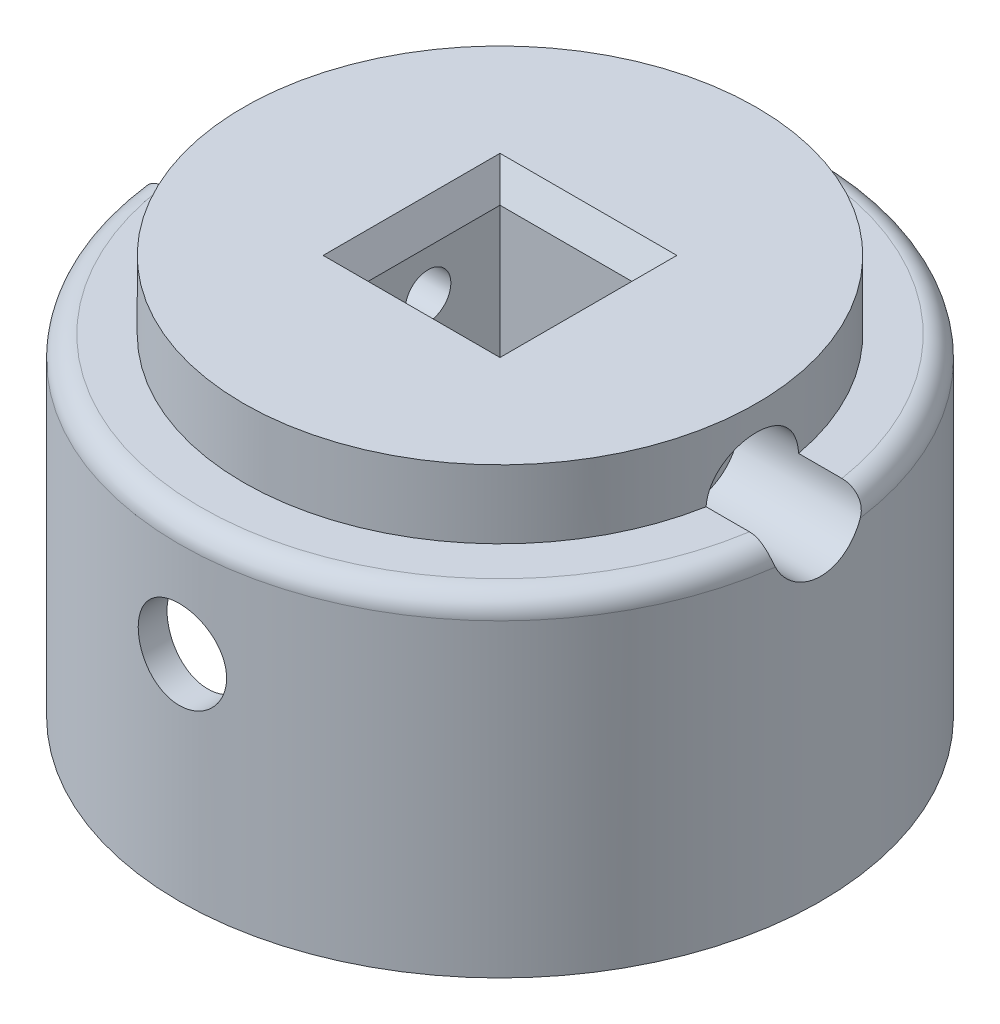
SolidWorks part; units mm, degrees
ref_plane "Спереди" through (0, 0, 0) normal (0, 0, 1) x (1, 0, 0)
ref_plane "Сверху" through (0, 0, 0) normal (0, 1, 0) x (1, 0, 0)
ref_plane "Справа" through (0, 0, 0) normal (1, 0, 0) x (0, 0, -1)
sketch "Sketch1" plane through (0, 0, 0) normal (0, 1, 0) x (1, 0, 0)
  circle A0 centre (0, 0) radius 22.5
  dimension "D1" = 45
extrude "Boss-Extrude1" add sketch "Sketch1" along normal blind 28
sketch "Sketch2" plane through (0, 0, 0) normal (0, -1, 0) x (1, 0, 0)
  line L1 (5.05, 5.05) -> (-5.05, 5.05)
  line L2 (5.05, 5.05) -> (5.05, -5.05)
  line L3 (5.05, -5.05) -> (-5.05, -5.05)
  line L4 (-5.05, 5.05) -> (-5.05, -5.05)
  line L5 (5.05, 5.05) -> (-5.05, -5.05) construction
  line L6 (5.05, -5.05) -> (-5.05, 5.05) construction
  point P0 (0, 0)
  dimension "D1" = 10.1
extrude "Cut-Extrude2" cut sketch "Sketch2" against normal through all
shell "Shell3" thickness 2 removed face at (0, 0, 0)
sketch "Sketch3" plane through (0, 0, 7.05) normal (0, 0, 1) x (1, 0, 0)
  line L0 (0, 26) -> (0, 0) construction
  line L1 (7.05, 26) -> (-7.05, 26) construction
  line L2 (7.05, 0) -> (-7.05, 0) construction
  line L3 (-22.5, 0) -> (22.5, 0) construction
  circle A0 centre (0, 15) radius 3.1
  dimension "D1" = 6.2
  dimension "D2" = 15
extrude "Cut-Extrude3" cut sketch "Sketch3" along normal through all
chamfer "Chamfer1" distance 2 angle 30 4 edges at (-5.05, 28, 0) (0, 28, 5.05) (5.05, 28, 0) (0, 28, -5.05) first distance on face at (-5.05, 14, 0) first distance on face at (0, 14, 5.05) first distance on face at (5.05, 14, 0) first distance on face at (0, 14, -5.05)
sketch "Sketch18" plane through (0, 26, 0) normal (0, -1, 0) x (1, 0, 0)
  line L0 (0, 0) -> (-18.4253, -8.9866) construction
  line L1 (0, 0) -> (-17.385, 10.8633) construction
  line L2 (0, 0) -> (0, -20.5) construction
  line L3 (-15.7289, -7.6715) -> (-18.4253, -8.9866)
  line L4 (-14.8408, 9.2736) -> (-17.385, 10.8633)
  circle A0 centre (0, 0) radius 20.5 construction
  arc A1 (-18.4253, -8.9866) -> (-17.385, 10.8633) centre (0, 0) cw
  arc A2 (-14.8408, 9.2736) -> (-15.7289, -7.6715) centre (0, 0) ccw
  dimension "D1" = 64
  dimension "D2" = 58
  dimension "D3" = 3
extrude "Boss-Extrude8" add sketch "Sketch18" along normal offset from surface (23 mm away) 3 up to face at (0, 0, 20.5)
sketch "Sketch9" plane through (0, 0, 0) normal (0, -1, 0) x (1, 0, 0)
  line L0 (0, -7.05) -> (0, -20.5) construction
  line L2 (2.0704, -22.4045) -> (-16.5877, -15.202)
  line L3 (-16.5877, -15.202) -> (-17.6681, -18.0007)
  line L4 (-17.6681, -18.0007) -> (0.99, -25.2032)
  line L5 (0.99, -25.2032) -> (2.0704, -22.4045)
  line L6 (-7.05, -7.05) -> (7.05, -7.05) construction
  line L7 (2.0704, -22.4045) -> (0, -7.05) construction
  circle A0 centre (0, 0) radius 22.5 construction
  circle A1 centre (0, 0) radius 20.5 construction
  dimension "D1" = 20
  dimension "D2" = 3
  dimension "D3" = 7.679
extrude "Boss-Extrude4" add sketch "Sketch9" against normal blind 20
sketch "Sketch11" plane through (0, 0, 0) normal (0, -1, 0) x (1, 0, 0)
  line L0 (2.0704, -22.4045) -> (7.05, -7.05)
  line L1 (7.05, -7.05) -> (-7.05, -7.05)
  line L2 (-7.05, -7.05) -> (-16.5877, -15.202)
  line L3 (-16.5877, -15.202) -> (2.0704, -22.4045) construction
  line L4 (-3.768, -20.1507) -> (-10.7492, -17.4558) construction
  arc A0 (2.0704, -22.4045) -> (-16.5877, -15.202) centre (0, 0) ccw construction
  arc A1 (2.0704, -22.4045) -> (-16.5877, -15.202) centre (0, 0) cw
  arc A2 (2.0704, -22.4045) -> (-16.5877, -15.202) centre (0, 0) ccw construction
  point P4 (-7.2586, -18.8032)
extrude "Boss-Extrude6" add sketch "Sketch11" against normal up to surface (26 mm away) up to face at (0, 26, 0)
sketch "Sketch12" plane through (0, 0, 0) normal (0, -1, 0) x (1, 0, 0)
  line L0 (-7.05, -7.05) -> (-15.0663, -13.9016) construction
  line L1 (2.748, -20.315) -> (7.05, -7.05) construction
  line L2 (3.7952, -17.0861) -> (2.748, -20.315)
  line L3 (-15.0663, -13.9016) -> (-12.7858, -11.9525)
  arc A0 (2.748, -20.315) -> (-15.0663, -13.9016) centre (0, 0) cw
  arc A1 (-12.7858, -11.9525) -> (3.7952, -17.0861) centre (0, 0) ccw
  arc A2 (2.748, -20.315) -> (-15.0663, -13.9016) centre (0, 0) ccw construction
  dimension "D1" = 3
extrude "Cut-Extrude5" cut sketch "Sketch12" against normal blind 12
sketch "Sketch17" plane through (0, 0, 0) normal (0, -1, 0) x (1, 0, 0)
  line L0 (7.05, 7.05) -> (7.05, -7.05)
  line L1 (7.05, -7.05) -> (3.7952, -17.0861)
  line L2 (7.05, 7.05) -> (-7.05, 7.05)
  line L3 (-7.05, 7.05) -> (-7.05, -7.05)
  line L4 (-7.05, -7.05) -> (-12.7858, -11.9525)
  arc A0 (3.7952, -17.0861) -> (-12.7858, -11.9525) centre (0, 0) cw
  arc A1 (-12.7858, -11.9525) -> (3.7952, -17.0861) centre (0, 0) ccw construction
extrude "Cut-Extrude9" cut sketch "Sketch17" against normal blind 2
sketch "Sketch20" plane through (0, 26, 0) normal (0, -1, 0) x (1, 0, 0)
  line L0 (2.748, -20.315) -> (7.05, -7.05)
  line L1 (7.05, -7.05) -> (7.05, 7.05)
  line L2 (7.05, 7.05) -> (-7.05, 7.05)
  line L3 (-7.05, 7.05) -> (-7.05, -7.05)
  line L4 (-7.05, -7.05) -> (-15.0663, -13.9016)
  arc A0 (2.748, -20.315) -> (-15.0663, -13.9016) centre (0, 0) ccw
  arc A1 (2.748, -20.315) -> (-17.385, 10.8633) centre (0, 0) ccw construction
extrude "Boss-Extrude10" add sketch "Sketch20" along normal blind 7
sketch "Sketch21" plane through (0, 28, 0) normal (0, 1, 0) x (1, 0, 0)
  circle A0 centre (0, 0) radius 18
  dimension "D1" = 36
extrude "Cut-Extrude11" cut sketch "Sketch21" against normal blind 4.8 flip side to cut
sketch "Sketch22" plane through (5.05, 0, 0) normal (-1, 0, 0) x (0, 0, 1)
  line L0 (0, 26) -> (0, 2) construction
  line L1 (5.05, 26) -> (-5.05, 26) construction
  line L2 (-5.05, 2) -> (5.05, 2) construction
  line L3 (-6.2047, 28) -> (6.2047, 28) construction
  circle A0 centre (0, 23) radius 1.6
  point P10 (0, 28)
  dimension "D1" = 3.2
  dimension "D2" = 5
extrude "Cut-Extrude12" cut sketch "Sketch22" against normal through all both and the other way through all
sketch "Sketch24" plane through (5.05, 0, 0) normal (-1, 0, 0) x (0, 0, 1)
  circle A0 centre (0, 23) radius 3.25
  dimension "D1" = 6.5
extrude "Cut-Extrude13" cut sketch "Sketch24" against normal through all from offset 8.5 offset against normal yes
sketch "Sketch25" plane through (-5.05, 0, 0) normal (1, 0, 0) x (0, 0, -1)
  line L0 (-5.05, 26) -> (-5.05, 2) construction
  line L1 (0, 19.75) -> (2.8146, 21.375)
  line L2 (2.8146, 21.375) -> (2.8146, 24.625)
  line L3 (2.8146, 24.625) -> (0, 26.25)
  line L4 (0, 26.25) -> (-2.8146, 24.625)
  line L5 (-2.8146, 24.625) -> (-2.8146, 21.375)
  line L6 (-2.8146, 21.375) -> (0, 19.75)
  circle A0 centre (0, 23) radius 3.25 construction
  dimension "D1" = 6.5
extrude "Cut-Extrude14" cut sketch "Sketch25" against normal through all from offset 8.5 offset against normal yes
fillet "Fillet1" radius 1.5 2 edges at (-0.2166, 23.2, 22.499) (-0.2166, 23.2, -22.499)
sketch "Sketch26" plane through (0, 0, 0) normal (0, -1, 0) x (1, 0, 0)
  circle A0 centre (0, 0) radius 22.5
  arc A1 (2.0704, -22.4045) -> (-16.5877, -15.202) centre (0, 0) ccw construction
  circle A2 centre (0, 0) radius 43.9199
extrude "Cut-Extrude15" cut sketch "Sketch26" against normal through all
chamfer "Chamfer2" distance 0.5 angle 70 4 edges at (-5.05, 2, 0) (0, 2, 5.05) (0, 2, -5.05) (5.05, 2, 0) first distance on face at (-1.612, 2, -5.2065)
